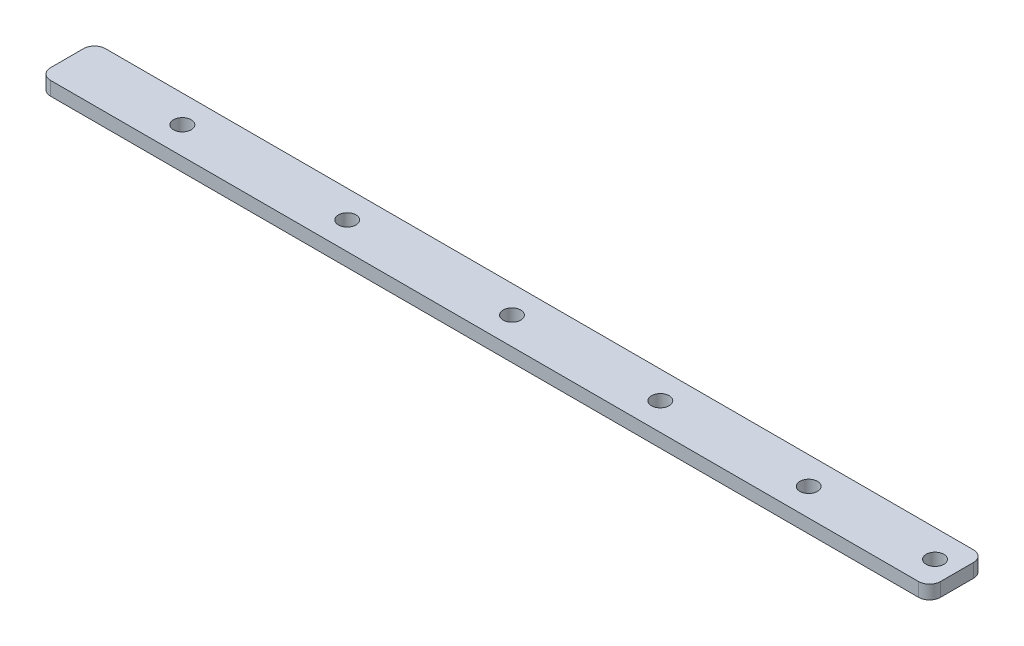
SolidWorks part; units mm, degrees
ref_plane "Front Plane" through (0, 0, 0) normal (0, 0, 1) x (1, 0, 0)
ref_plane "Top Plane" through (0, 0, 0) normal (0, 1, 0) x (1, 0, 0)
ref_plane "Right Plane" through (0, 0, 0) normal (1, 0, 0) x (0, 0, -1)
sketch "Sketch1" plane through (0, 0, 0) normal (0, 1, 0) x (1, 0, 0)
  line L1 (-102.87, -6.35) -> (102.87, -6.35)
  line L2 (-102.87, -6.35) -> (-102.87, 6.35)
  line L3 (-102.87, 6.35) -> (102.87, 6.35)
  line L4 (102.87, -6.35) -> (102.87, 6.35)
  line L5 (-102.87, -6.35) -> (102.87, 6.35) construction
  line L6 (-102.87, 6.35) -> (102.87, -6.35) construction
  point P0 (0, 0)
  dimension "D1" = 205.74
  dimension "D2" = 12.7
extrude "Boss-Extrude1" add sketch "Sketch1" along normal blind 3.175 contours L2 L3 L4 L1
fillet "Fillet1" radius 2.54 4 edges at (102.87, 1.5875, -6.35) (102.87, 1.5875, 6.35) (-102.87, 1.5875, 6.35) (-102.87, 1.5875, -6.35)
sketch "Sketch2" plane through (0, 3.175, 0) normal (0, 1, 0) x (1, 0, 0)
  line L0 (-102.87, 0) -> (102.87, 0) construction
  line L1 (-102.87, -3.81) -> (-102.87, 3.81) construction
  line L2 (102.87, -3.81) -> (102.87, 3.81) construction
  circle A0 centre (-76.2, 0) radius 2.032
  circle A1 centre (0, 0) radius 2.032
  circle A2 centre (-38.1, 0) radius 2.032
  circle A3 centre (97.79, 0) radius 2.032
  circle A4 centre (68.58, 0) radius 2.032
  circle A5 centre (34.29, 0) radius 2.032
  dimension "D1" = 4.064
  dimension "D2" = 5.08
  dimension "D3" = 34.29
  dimension "D4" = 38.1
  dimension "D5" = 76.2
  dimension "D6" = 34.29
extrude "Cut-Extrude1" cut sketch "Sketch2" against normal up to next
